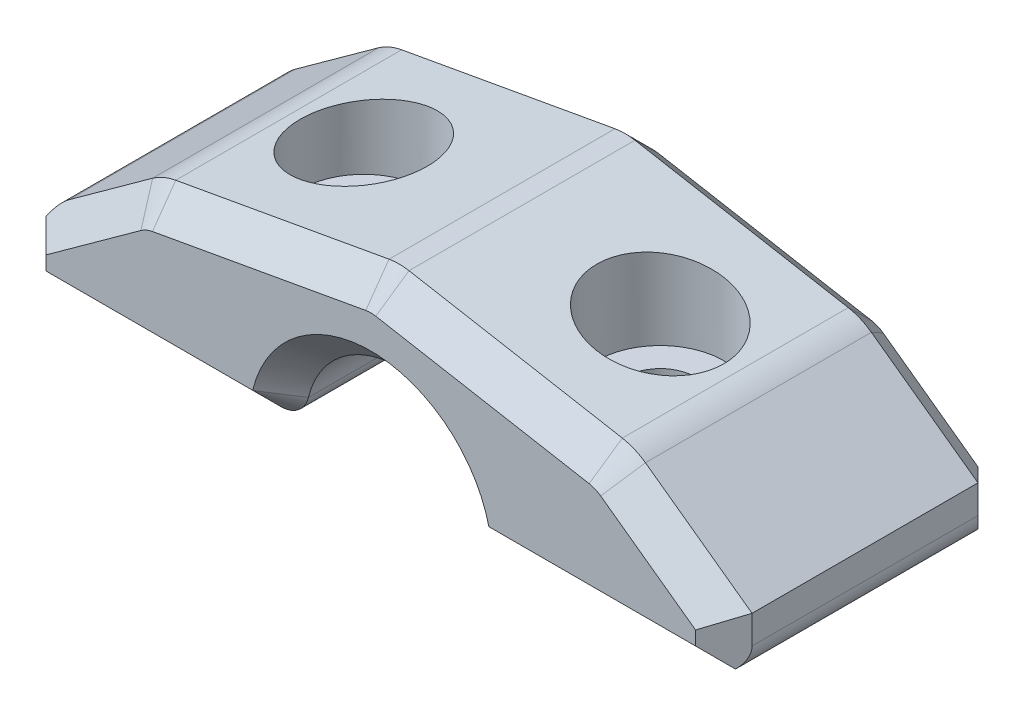
SolidWorks part; units mm, degrees
ref_plane "Front Plane" through (0, 0, 0) normal (0, 0, 1) x (1, 0, 0)
ref_plane "Top Plane" through (0, 0, 0) normal (0, 1, 0) x (1, 0, 0)
ref_plane "Right Plane" through (0, 0, 0) normal (1, 0, 0) x (0, 0, -1)
sketch "Sketch1" plane through (0, 0, 0) normal (0, 0, 1) x (1, 0, 0)
  line L0 (-3.3, 0) -> (-12.5, 0)
  line L1 (-12.5, 0) -> (-12.5, 6.5)
  line L2 (-12.5, 6.5) -> (12.5, 6.5)
  line L3 (0, 6.5) -> (0, 3.3) construction
  line L4 (12.5, 0) -> (12.5, 6.5)
  line L5 (3.3, 0) -> (12.5, 0)
  arc A0 (3.3, 0) -> (-3.3, 0) centre (0, 0) ccw
  dimension "D1" = 6.6
  dimension "D2" = 25
  dimension "D3" = 6.5
extrude "Boss-Extrude1" add sketch "Sketch1" along normal blind 10
sketch "Sketch2" plane through (0, 0, 10) normal (0, 0, 1) x (1, 0, 0)
  line L0 (0, 6.5) -> (-8.3557, 5)
  line L1 (12.5, 6.5) -> (-12.5, 6.5) construction
  line L2 (-8.3557, 5) -> (-12.5, 2.0044)
  line L3 (-12.5, 6.5) -> (-12.5, 0) construction
  line L4 (-12.5, 2.0044) -> (-12.5, 6.5)
  line L5 (-12.5, 6.5) -> (12.5, 6.5)
  line L6 (0, 8.1862) -> (0, -3.9101) construction
  line L7 (12.5, 2.0044) -> (12.5, 6.5)
  line L8 (8.3557, 5) -> (12.5, 2.0044)
  line L9 (0, 6.5) -> (8.3557, 5)
  line L10 (-12.5, 0) -> (-3.3, 0) construction
  line M8 (12.5, 0) -> (12.5, 6.5)
  line M9 (12.5, 6.5) -> (-12.5, 6.5)
  line M10 (-12.5, 6.5) -> (-12.5, 0)
  dimension "D1" = 5
  dimension "D2" = 16.7114
  dimension "D3" = 4.4956
extrude "Cut-Extrude1" cut sketch "Sketch2" against normal through all both and the other way through all contours L2 L0 M9 M10 | L9 L8 M9 M8 region at (-9.0286, 5.2531, 10) region at (9.0286, 5.2531, 10)
chamfer "Chamfer1" distance 1 angle 45 4 edges at (-12.5, 1.0022, 0) (12.5, 1.0022, 0) (12.5, 1.0022, 10) (-12.5, 1.0022, 10)
fillet "Fillet3" radius 1 4 edges at (12.5, 0, 5) (3.3, 0, 5) (-12.5, 0, 5) (-3.3, 0, 5)
sketch "Sketch4" plane through (0, 0, 0) normal (0, -1, 0) x (1, 0, 0)
  line L0 (0, 10) -> (0, 0) construction
  line L1 (-5.25, 5) -> (5.25, 5) construction
  line L2 (3.2095, 10) -> (-3.2095, 10) construction
  line L4 (-3.2095, 0) -> (3.2095, 0) construction
  circle A0 centre (-5.25, 5) radius 1.25
  circle A1 centre (5.25, 5) radius 1.25
  point P8 (0, 5)
  point P17 (0, 5)
  dimension "D2" = 2.5
  dimension "D1" = 10.5
extrude "Cut-Extrude2" cut sketch "Sketch4" against normal through all
sketch "Sketch5" plane through (0, 0, 0) normal (0, 1, 0) x (1, 0, 0)
  circle A0 centre (-5.25, -5) radius 2.25
  circle A1 centre (5.25, -5) radius 2.25
  dimension "D1" = 4.5
extrude "Cut-Extrude3" cut sketch "Sketch5" along normal blind 10 from offset 3
fillet "Fillet2" radius 2 4 edges at (8.3557, 5, 5) (-8.3557, 5, 5) (0, 6.5, 5) (-12.5, 2.0044, 5)
chamfer "Chamfer2" distance 1 angle 45 12 edges at (-10.1126, 3.7301, 0) (-8.3356, 4.9528, 0) (-4.1302, 5.7586, 0) (10.1126, 3.7301, 0) (0, 6.468, 0) (8.3356, 4.9528, 0) (4.1302, 5.7586, 0) (0, 3.3, 0) (-7.8411, 0, 0) (7.8411, 0, 0) (-3.5627, 0.215, 0) (3.5627, 0.215, 0)
chamfer "Chamfer3" distance 1 angle 45 12 edges at (-10.1126, 3.7301, 10) (-7.8411, 0, 10) (-3.5627, 0.215, 10) (0, 3.3, 10) (3.5627, 0.215, 10) (7.8411, 0, 10) (-8.3356, 4.9528, 10) (-4.1302, 5.7586, 10) (10.1126, 3.7301, 10) (0, 6.468, 10) (8.3356, 4.9528, 10) (4.1302, 5.7586, 10)
